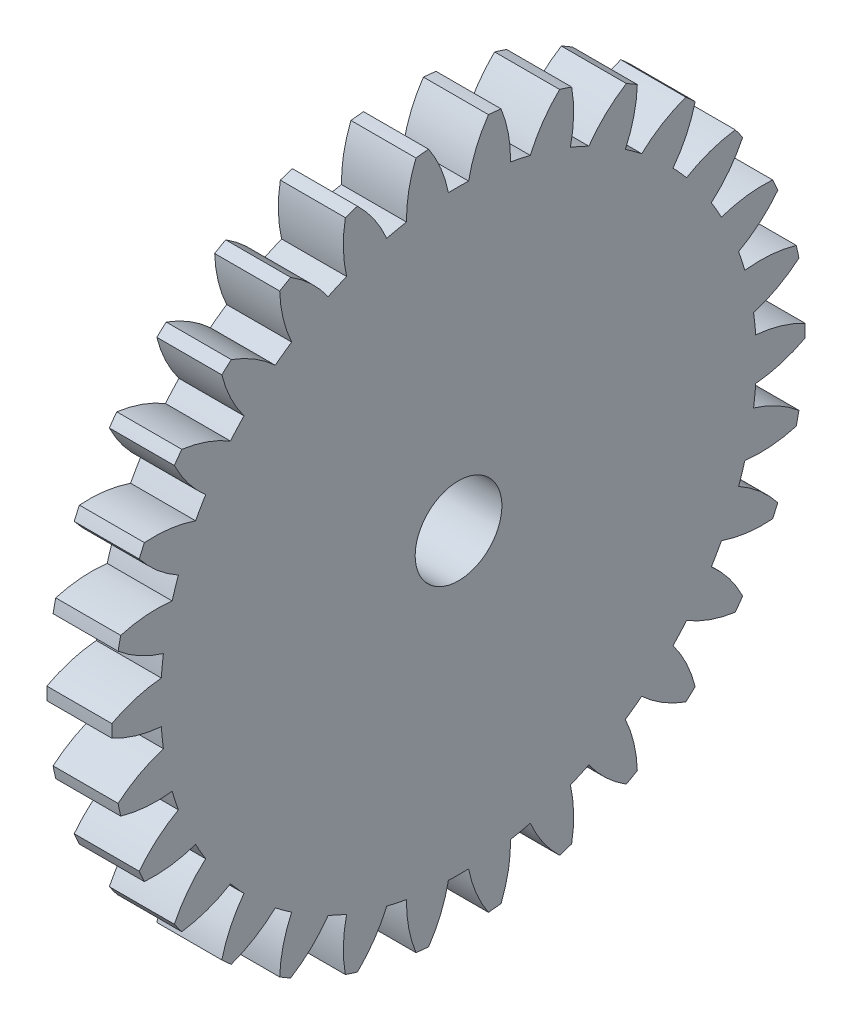
SolidWorks part; units mm, degrees
material "ﾎﾟﾘｵｷｼﾒﾁﾚﾝ(POM)ｱｾﾀｰﾙ共重合体"
ref_plane "Plane1" through (0, 0, 0) normal (0, 0, 1) x (1, 0, 0)
ref_plane "Plane2" through (0, 0, 0) normal (0, 1, 0) x (1, 0, 0)
ref_plane "Plane3" through (0, 0, 0) normal (1, 0, 0) x (0, 0, -1)
other "Configuration Table"
sketch "HoldingSke" plane through (0, 0, 0) normal (0, 1, 0) x (1, 0, 0)
  line L0 (0, 0) -> (0.866, -0.5)
  line L1 (-15, 0) -> (100, 0) construction
  line L2 (0, 0) -> (-2.1039, 2.3779)
  line L3 (0, 0) -> (-11.863, 4.5341)
  line L4 (0, 0) -> (7.479, 4.318)
  line L5 (0, 0) -> (-46.8476, -17.4728)
  line L6 (0, 0) -> (-2.4869, -1.6779)
  line L7 (-2.1039, 2.3779) -> (8.6586, 51.2059)
  line L8 (-76.2, 54.61) -> (-75.2, 54.61)
  line L9 (-71.009, 38.7566) -> (-53.1078, 45.2721)
  line L10 (-76.2, 71.12) -> (104.1128, 71.12)
  line L11 (0, 0) -> (-3, 0)
  line L12 (-76.2, 101.6) -> (-76.162, 101.6)
  line L13 (24.9733, 27.94) -> (52.9518, 28.4284)
  line L14 (24.9733, 27.94) -> (24.9743, 27.94)
  line L15 (24.9733, 27.94) -> (100.4006, 29.5858)
  line L16 (-63.627, -1) -> (-12.827, -1)
  circle A0 centre (0, 0) radius 4
  circle A1 centre (0, 0) radius 13.749
  circle A2 centre (0, 0) radius 37.5
  circle A3 centre (0, 0) radius 4
  dimension "MHD" = 27.498
  dimension "Hub_dia" = 75
  dimension "Bore" = 8
  dimension "MBD" = 8
  dimension "Num_teeth" = 30
  dimension "Pitch" = 1
  dimension "Overall_len" = 50
  dimension "Show_teeth" = 30
  dimension "Thickness" = 3
  dimension "OAL" = 50.0001
  dimension "T_dim" = 1
  dimension "Ap" = 20
  dimension "H" = 19.05
  dimension "Pitch_radius" = 180.3128
  dimension "Width" = 3
  dimension "Backlash" = 0.038
  dimension "Addendum_fac" = 1
  dimension "Dedendum_fac" = 1.25
  dimension "Clearance_fac" = 0.25
  dimension "Dedendum_add" = 0.001
  dimension "Module" = 1
sketch "BasProSke" plane through (0, 0, 0) normal (0, 1, 0) x (1, 0, 0)
  line L0 (-10, 0) -> (60, 0) construction
  line L1 (0, 0) -> (0, 16)
  line L2 (0, 0) -> (3, 0)
  line L3 (3, 0) -> (3, 16)
  line L4 (3, 16) -> (0, 16)
  dimension "Thickness" = 3
  dimension "Diameter" = 32
revolve "Base-Revolve" add sketch "BasProSke" angle 360 about L0
sketch "TooCutSke" plane through (0, 0, 0) normal (1, 0, 0) x (0, 0, -1)
  line L1 (0, 0) -> (0, 107) construction
  line L2 (0, 0) -> (-0.8515, 14.9758) construction
  line L3 (0, 0) -> (-3.1323, 29.8014) construction
  line L4 (-0.8515, 14.9758) -> (-1.5661, 14.9007) construction
  arc A0 (0.4664, 13.7411) -> (-0.4664, 13.7411) centre (0, 0) ccw
  arc A1 (1.3975, 15.9644) -> (-1.3975, 15.9644) centre (0, 0) ccw
  circle A2 centre (0, 0) radius 15 construction
  circle A3 centre (0, 0) radius 14.0954 construction
  arc A4 (-0.4664, 13.7411) -> (-1.3975, 15.9644) centre (-6.3534, 12.5823) ccw
  arc A5 (1.3975, 15.9644) -> (0.4664, 13.7411) centre (6.3534, 12.5823) ccw
  dimension "Root_dia" = 27.498
  dimension "Overcut_dia" = 32.0508
  dimension "Pitch_dia" = 30
  dimension "Base_dia" = 28.1908
  dimension "Flank_rad" = 6
  dimension "Half_ang" = 6
  dimension "Half_CT" = 0.7185
extrude "ToothCut" cut sketch "TooCutSke" along normal through all
fillet "Breaks" [suppressed] radius 0.02 tangent propagation no
fillet "RootFillets" [suppressed] radius 0.251
pattern_circular "TeethCuts" count 30 every 12 about axis through (-10, 0, 0) along (1, 0, 0) of "ToothCut", "RootFillets", "Breaks"
sketch "HubNeaOneSke" plane through (0, 0, 0) normal (-1, 0, 0) x (0, 0, 1)
  circle A0 centre (0, 0) radius 13.749
  dimension "Diameter" = 27.498
extrude "HubNearOne" [suppressed] add sketch "HubNeaOneSke" along normal blind 47.0001
sketch "HubNeaBotSke" plane through (0, 0, 0) normal (-1, 0, 0) x (0, 0, 1)
  circle A0 centre (0, 0) radius 13.749
  dimension "Diameter" = 27.498
extrude "HubNearBoth" [suppressed] add sketch "HubNeaBotSke" along normal blind 23.5
ref_plane "FarPln" through (3, 0, 0) normal (1, 0, 0) x (0, 0, -1)
sketch "HubFarSke" plane through (3, 0, 0) normal (1, 0, 0) x (0, 0, -1)
  circle A0 centre (0, 0) radius 13.749
  dimension "Diameter" = 27.498
extrude "HubFar" [suppressed] add sketch "HubFarSke" along normal blind 23.5
sketch "BorSke" plane through (0, 0, 0) normal (1, 0, 0) x (0, 0, -1)
  circle A0 centre (0, 0) radius 4
  dimension "Diameter" = 8
extrude "Bore" cut sketch "BorSke" along normal mid plane 100.0001
sketch "KeySke" plane through (0, 0, 0) normal (1, 0, 0) x (0, 0, -1)
  line L0 (-1, 0) -> (-1, 5)
  line L1 (-1, 5) -> (1, 5)
  line L2 (1, 5) -> (1, 0)
  line L3 (0, 0) -> (0, 34) construction
  line L4 (-1, 0) -> (1, 0)
  dimension "Offset" = 5
  dimension "Width" = 2
extrude "Keyway" [suppressed] cut sketch "KeySke" along normal mid plane 100.0001
pattern_circular "Keyway2" [suppressed] count 2 every 90 about axis through (-10, 0, 0) along (1, 0, 0) reverse direction yes
sketch "ｽｹｯﾁ1" plane through (0, 0, 0) normal (-1, 0, 0) x (0, 0, 1)
  circle A0 centre (0, 0) radius 4 construction
  circle A1 centre (0, 0) radius 4
extrude "ﾎﾞｽ - 押し出し1" add sketch "ｽｹｯﾁ1" against normal up to surface (3 mm away) up to face at (3, 0, 4)
sketch "ｽｹｯﾁ2" plane through (0, 0, 0) normal (-1, 0, 0) x (0, 0, 1)
  circle A0 centre (0, 0) radius 2
  dimension "D1" = 4
extrude "ｶｯﾄ - 押し出し1" cut sketch "ｽｹｯﾁ2" against normal through all
equation "' \"Module@HoldingSke\" = 6.35"
equation "' \"Num_teeth@HoldingSke\" = 12"
equation "' \"Ap@HoldingSke\" =  20"
equation "' \"Ap@HoldingSke\" = 20"
equation "' \"Width@HoldingSke\" = 0.5 * 25.4"
equation "' \"Hub_dia@HoldingSke\"= 1 * 25.4"
equation "' \"Hub_dia@HoldingSke\" = 1 * 25.4"
equation "' \"Overall_len@HoldingSke\" = 1.0 * 25.4"
equation "' \"Bore@HoldingSke\" = 0.75 * 25.4"
equation "' \"T_dim@HoldingSke\" = 0.1 * 25.4"
equation "' \"Width@KeySke\" = 0.25 * 25.4"
equation "' \"Show_teeth@HoldingSke\" = 13"
equation "' \"Backlash@HoldingSke\" = 0.009 * 25.4"
equation "' \"Addendum_fac@HoldingSke\" = 1.0"
equation "' \"Dedendum_fac@HoldingSke\" = 1.25"
equation "' \"Dedendum_add@HoldingSke\" = 0.00005 * 25.4"
equation "' \"Clearance_fac@HoldingSke\" = 0.25"
equation "\"Pitch@HoldingSke\" = 1 / \"Module@HoldingSke\""
equation "\"Overcut_dia@TooCutSke\" = (\"Num_teeth@HoldingSke\" + 2 * \"Addendum_fac@HoldingSke\") / \"Pitch@HoldingSke\" + 0.002 * 25.4"
equation "\"Pitch_dia@TooCutSke\" = \"Num_teeth@HoldingSke\" / \"Pitch@HoldingSke\""
equation "\"Base_dia@TooCutSke\" = \"Num_teeth@HoldingSke\" / \"Pitch@HoldingSke\" * cos((\"Ap@HoldingSke\"  * 3.14159265 / 180))"
equation "\"Root_dia@TooCutSke\" = (\"Num_teeth@HoldingSke\" + 2) / \"Pitch@HoldingSke\" - 2 * (\"Addendum_fac@HoldingSke\" + \"Dedendum_fac@HoldingSke\") / \"Pitch@HoldingSke\" - \"Dedendum_add@HoldingSke\" * 2"
equation "\"Half_ang@TooCutSke\" = 180 / \"Num_teeth@HoldingSke\""
equation "\"Half_CT@TooCutSke\" = \"Num_teeth@HoldingSke\" / \"Pitch@HoldingSke\" * sin((3.14159265 / 2 / \"Num_teeth@HoldingSke\")) / 2 - 7 * \"Backlash@HoldingSke\" / 4"
equation "\"Flank_rad@TooCutSke\" = \"Num_teeth@HoldingSke\" / \"Pitch@HoldingSke\" / 5"
equation "\"Radius@RootFillets\" = \"Clearance_fac@HoldingSke\" / \"Pitch@HoldingSke\" + \"Dedendum_add@HoldingSke\""
equation "\"Break_rad@Breaks\" = 0.02 / \"Pitch@HoldingSke\""
equation "\"Thickness@HoldingSke\" = \"Width@HoldingSke\""
equation "\"OAL@HoldingSke\" = \"Thickness@HoldingSke\""
equation "\"MHD@HoldingSke\" = (\"Num_teeth@HoldingSke\" + 2) / \"Pitch@HoldingSke\" - 2 * (\"Addendum_fac@HoldingSke\" + \"Dedendum_fac@HoldingSke\")  / \"Pitch@HoldingSke\" - \"Dedendum_add@HoldingSke\" * 2"
equation "\"MBD@HoldingSke\" = (\"Num_teeth@HoldingSke\" + 2) / \"Pitch@HoldingSke\" - 2 * (\"Addendum_fac@HoldingSke\" + \"Dedendum_fac@HoldingSke\")  / \"Pitch@HoldingSke\" - \"Dedendum_add@HoldingSke\" * 2 - 0.002 * 25.4"
equation "\"MHD@HoldingSke\" = ((sgn( \"MHD@HoldingSke\" - \"Hub_dia@HoldingSke\" )-1)*( \"MHD@HoldingSke\" - \"Hub_dia@HoldingSke\" ))/-2+ \"Hub_dia@HoldingSke\""
equation "\"MBD@HoldingSke\" = ((sgn( \"MBD@HoldingSke\" - \"Bore@HoldingSke\" )-1)*( \"MBD@HoldingSke\" - \"Bore@HoldingSke\" ))/-2+ \"Bore@HoldingSke\""
equation "\"OAL@HoldingSke\" = ((sgn( \"OAL@HoldingSke\" - \"Overall_len@HoldingSke\" )+1)*( \"OAL@HoldingSke\" - \"Overall_len@HoldingSke\" ))/2 + \"Overall_len@HoldingSke\" + 0.000002 * 25.4"
equation "\"Num_teeth@TeethCuts\" = int( \"Show_teeth@HoldingSke\" ) + 1"
equation "\"Num_teeth@TeethCuts\" = ((sgn( \"Num_teeth@TeethCuts\" - \"Num_teeth@HoldingSke\" )-1)*( \"Num_teeth@TeethCuts\" - \"Num_teeth@HoldingSke\" ))/-2+ \"Num_teeth@HoldingSke\""
equation "\"Num_teeth@TeethCuts\" = ((sgn( \"Num_teeth@TeethCuts\" - 2.0)+1)*( \"Num_teeth@TeethCuts\" - 2.0))/2 +2.0"
equation "\"Angle@TeethCuts\" = 360.0 / \"Num_teeth@HoldingSke\""
equation "\"Diameter@BasProSke\" = (\"Num_teeth@HoldingSke\" + 2 * \"Addendum_fac@HoldingSke\") / \"Pitch@HoldingSke\""
equation "\"Thickness@BasProSke\"  = \"Thickness@HoldingSke\""
equation "' \"Fillet_rad@BasProSke\" =  \"Thickness@HoldingSke\" * 0.05"
equation "' \"Fillet_rad@BasProSke\" = \"Thickness@HoldingSke\" * 0.05"
equation "\"MHD@HoldingSke\" = ((sgn( \"MHD@HoldingSke\" - \"Root_dia@TooCutSke\" )-1)*( \"MHD@HoldingSke\" - \"Root_dia@TooCutSke\" ))/-2+ \"Root_dia@TooCutSke\""
equation "\"Diameter@HubNeaOneSke\" = \"MHD@HoldingSke\""
equation "\"Length@HubNearOne\" = \"OAL@HoldingSke\" - \"Thickness@BasProSke\""
equation "\"Diameter@HubNeaBotSke\" = \"MHD@HoldingSke\""
equation "\"Length@HubNearBoth\" = ( \"OAL@HoldingSke\" - \"Thickness@BasProSke\" ) / 2.0"
equation "\"Thickness@FarPln\" = \"Thickness@BasProSke\""
equation "\"Diameter@HubFarSke\" = \"MHD@HoldingSke\""
equation "\"Length@HubFar\" = ( \"OAL@HoldingSke\" - \"Thickness@BasProSke\" ) / 2.0"
equation "\"Diameter@BorSke\" = \"MBD@HoldingSke\""
equation "\"D1@Bore\" = \"OAL@HoldingSke\" * 2.0"
equation "\"D1@Keyway\" = \"OAL@HoldingSke\" * 2.0"
equation "\"Offset@KeySke\" = \"T_dim@HoldingSke\" + \"MBD@HoldingSke\" / 2.0"
